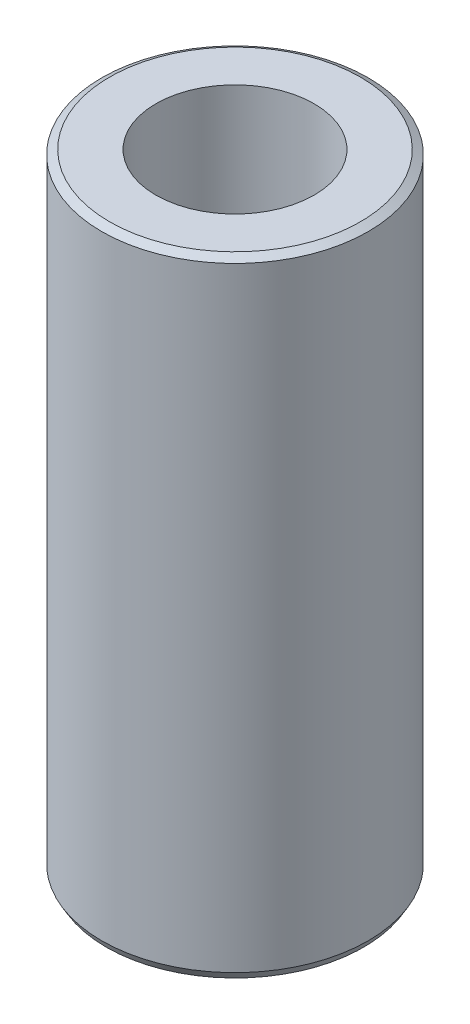
SolidWorks part; units mm, degrees
ref_plane "Front Plane" through (0, 0, 0) normal (0, 0, 1) x (1, 0, 0)
ref_plane "Top Plane" through (0, 0, 0) normal (0, 1, 0) x (1, 0, 0)
ref_plane "Right Plane" through (0, 0, 0) normal (1, 0, 0) x (0, 0, -1)
sketch "Sketch1" plane through (0, 0, 0) normal (0, 1, 0) x (1, 0, 0)
  circle A0 centre (0, 0) radius 35
  dimension "SHAFT_OD" = 70
extrude "Boss-Extrude1" add sketch "Sketch1" along normal blind 164.5874
sketch "Sketch2" plane through (0, 0, 0) normal (0, 1, 0) x (1, 0, 0)
  circle A0 centre (0, 0) radius 20.7968
  dimension "BORE_D" = 41.5937
extrude "Cut-Extrude1" cut sketch "Sketch2" along normal through all
chamfer "Chamfer1" distance 1.1911 angle 60 2 edges at (0, 164.5874, 35) (0, 0, 35) first distance on face at (0, 164.5874, 35) first distance on face at (0, 0, 20.7968)
